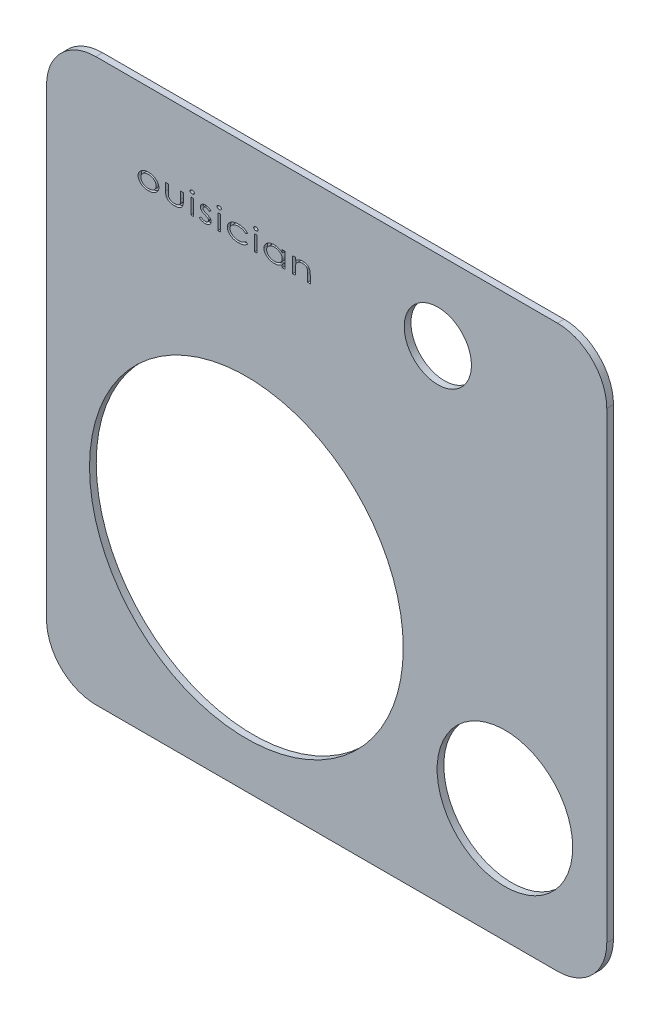
SolidWorks part; units mm, degrees
material "Pine"
ref_plane "Front Plane" through (0, 0, 0) normal (0, 0, 1) x (1, 0, 0)
ref_plane "Top Plane" through (0, 0, 0) normal (0, 1, 0) x (1, 0, 0)
ref_plane "Right Plane" through (0, 0, 0) normal (1, 0, 0) x (0, 0, -1)
sketch "Sketch1" plane through (0, 0, 0) normal (0, 0, 1) x (1, 0, 0)
  line L1 (0, 0) -> (500, 0)
  line L2 (0, 0) -> (0, 501)
  line L3 (0, 501) -> (500, 501)
  line L4 (500, 0) -> (500, 501)
  dimension "D1" = 500
  dimension "D2" = 501
extrude "Boss-Extrude1" add sketch "Sketch1" along normal blind 6
fillet "Fillet1" radius 44 4 edges at (0, 0, 3) (500, 0, 3) (0, 501, 3) (500, 501, 3)
sketch "Sketch2" plane through (0, 0, 6) normal (0, 0, 1) x (1, 0, 0)
  circle A0 centre (178.369, 181.0347) radius 156
  dimension "D1" = 312
sketch "Sketch3" plane through (0, 0, 6) normal (0, 0, 1) x (1, 0, 0)
  circle A1 centre (178.369, 181.0347) radius 140
  dimension "D1" = 280
extrude "Cut-Extrude2" cut sketch "Sketch3" against normal through all
sketch "Sketch4" plane through (0, 0, 6) normal (0, 0, 1) x (1, 0, 0)
  circle A0 centre (409.1034, 102.5162) radius 72.5
  dimension "D1" = 145
sketch "Sketch5" plane through (0, 0, 6) normal (0, 0, 1) x (1, 0, 0)
  circle A0 centre (409.1034, 102.5162) radius 60.5
  dimension "D1" = 121
extrude "Cut-Extrude3" cut sketch "Sketch5" against normal through all
sketch "Sketch6" plane through (0, 0, 6) normal (0, 0, 1) x (1, 0, 0)
  line L0 (500, 360) -> (0, 360)
  line L1 (500, 44) -> (500, 457) construction
  line L2 (0, 457) -> (0, 44) construction
  line L3 (44, 0) -> (456, 0) construction
  line L4 (456, 501) -> (44, 501) construction
  circle A0 centre (349.2286, 430) radius 50
  circle A1 centre (349.2286, 430) radius 30
  dimension "D1" = 100
  dimension "D3" = 60
  dimension "D2" = 360
  dimension "D4" = 71
extrude "Cut-Extrude5" cut sketch "Sketch6" against normal through all contours A1 region at (349.2286, 430, 6)
sketch "Sketch7" plane through (0, 0, 6) normal (0, 0, 1) x (1, 0, 0)
  line L0 (0, 457) -> (0, 44) construction
  line L1 (456, 501) -> (44, 501) construction
  text T0 "ouisician" font "Century Gothic" height in points 72
  point P1 (0, 0)
  point P2 (0, 0)
  point P3 (0, 0)
  dimension "D1" = 80
  dimension "D2" = 80
extrude "Cut-Extrude6" cut sketch "Sketch7" against normal blind 3
